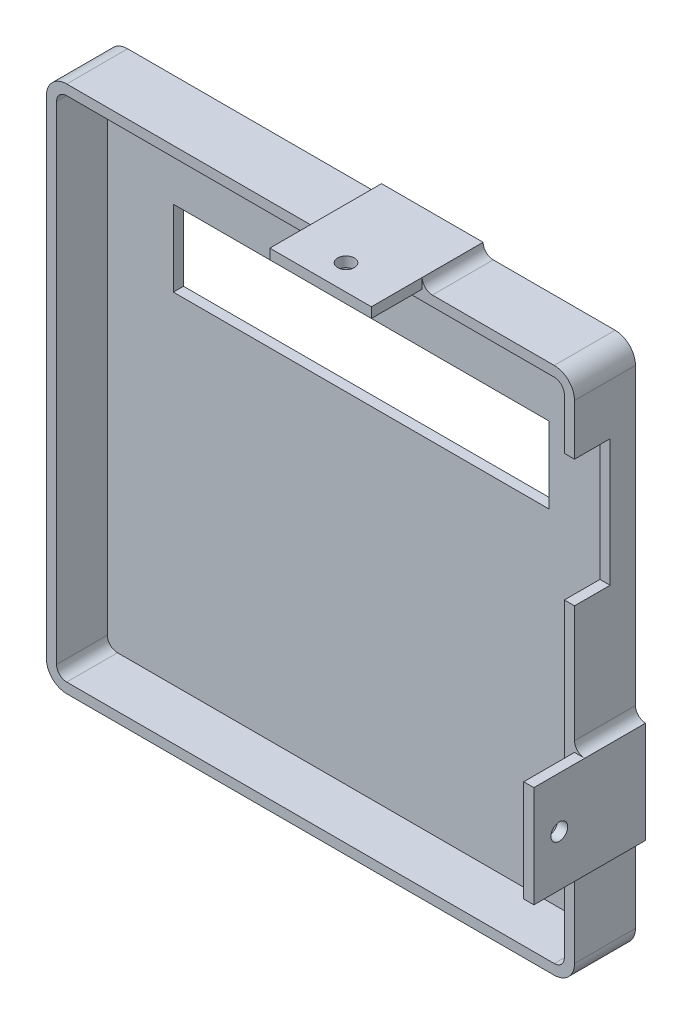
SolidWorks part; units mm, degrees
ref_plane "前视基准面" through (0, 0, 0) normal (0, 0, 1) x (1, 0, 0)
ref_plane "上视基准面" through (0, 0, 0) normal (0, 1, 0) x (1, 0, 0)
ref_plane "右视基准面" through (0, 0, 0) normal (1, 0, 0) x (0, 0, -1)
sketch "草图1" plane through (0, 0, 0) normal (0, 0, 1) x (1, 0, 0)
  line L1 (4, 0) -> (100, 0)
  line L2 (0, 4) -> (0, 100)
  line L3 (4, 104) -> (100, 104)
  line L4 (104, 4) -> (104, 100)
  arc A0 (100, 0) -> (104, 4) centre (100, 4) ccw
  arc A1 (100, 104) -> (104, 100) centre (100, 100) cw
  arc A2 (0, 100) -> (4, 104) centre (4, 100) cw
  arc A3 (4, 0) -> (0, 4) centre (4, 4) cw
  point P7 (104, 0)
  point P12 (0, 104)
  point P15 (0, 0)
  dimension "D3" = 4
  dimension "D1" = 104
  dimension "D2" = 104
extrude "凸台-拉伸2" add sketch "草图1" along normal blind 2
sketch "草图4" plane through (0, 0, 2) normal (0, 0, 1) x (1, 0, 0)
  line L4 (104, 4) -> (104, 100)
  line L5 (100, 104) -> (4, 104)
  line L6 (0, 100) -> (0, 4)
  line L7 (4, 0) -> (100, 0)
  line L8 (104, 4) -> (104, 100)
  line L9 (100, 104) -> (4, 104)
  line L10 (0, 100) -> (0, 4)
  line L11 (4, 0) -> (100, 0)
  line L16 (102, 4) -> (102, 100)
  line L17 (100, 102) -> (4, 102)
  line L18 (2, 100) -> (2, 4)
  line L19 (4, 2) -> (100, 2)
  line L20 (102, 4) -> (102, 100)
  line L21 (100, 102) -> (4, 102)
  line L22 (2, 100) -> (2, 4)
  line L23 (4, 2) -> (100, 2)
  arc A4 (100, 0) -> (104, 4) centre (100, 4) ccw
  arc A5 (104, 100) -> (100, 104) centre (100, 100) ccw
  arc A6 (4, 104) -> (0, 100) centre (4, 100) ccw
  arc A7 (0, 4) -> (4, 0) centre (4, 4) ccw
  arc A8 (100, 0) -> (104, 4) centre (100, 4) ccw
  arc A9 (104, 100) -> (100, 104) centre (100, 100) ccw
  arc A10 (4, 104) -> (0, 100) centre (4, 100) ccw
  arc A11 (0, 4) -> (4, 0) centre (4, 4) ccw
  arc A16 (100, 2) -> (102, 4) centre (100, 4) ccw
  arc A17 (102, 100) -> (100, 102) centre (100, 100) ccw
  arc A18 (4, 102) -> (2, 100) centre (4, 100) ccw
  arc A19 (2, 4) -> (4, 2) centre (4, 4) ccw
  arc A20 (100, 2) -> (102, 4) centre (100, 4) ccw
  arc A21 (102, 100) -> (100, 102) centre (100, 100) ccw
  arc A22 (4, 102) -> (2, 100) centre (4, 100) ccw
  arc A23 (2, 4) -> (4, 2) centre (4, 4) ccw
  dimension "D1" = 0
  dimension "D2" = 2
extrude "凸台-拉伸3" add sketch "草图4" along normal blind 10
sketch "草图5" plane through (104, 0, 0) normal (1, 0, 0) x (0, 0, -1)
  line L0 (-12, 4) -> (-12, 100) construction
  line L1 (-12, 90) -> (-5, 90)
  line L2 (-12, 90) -> (-12, 65)
  line L3 (-12, 65) -> (-5, 65)
  line L4 (-5, 90) -> (-5, 65)
  line L5 (-12, 100) -> (0, 100) construction
  dimension "D1" = 10
  dimension "D2" = 25
  dimension "D3" = 7
extrude "切除-拉伸1" cut sketch "草图5" against normal blind 10
sketch "草图6" plane through (0, 0, 0) normal (0, 0, -1) x (-1, 0, 0)
  line L0 (-100, 104) -> (-4, 104) construction
  line L1 (-15, 69) -> (-89, 69)
  line L2 (-15, 69) -> (-15, 84)
  line L3 (-15, 84) -> (-89, 84)
  line L4 (-89, 69) -> (-89, 84)
  line L5 (0, 100) -> (0, 4) construction
  line L6 (-104, 4) -> (-104, 100) construction
  dimension "D1" = 20
  dimension "D2" = 15
  dimension "D3" = 15
  dimension "D4" = 15
extrude "切除-拉伸2" cut sketch "草图6" against normal blind 10
sketch "草图7" plane through (0, 0, 0) normal (0, 0, -1) x (-1, 0, 0)
  line L0 (-100, 104) -> (-4, 104) construction
  line L1 (-74, 104) -> (-54, 104)
  line L2 (-74, 104) -> (-74, 106)
  line L3 (-74, 106) -> (-54, 106)
  line L4 (-54, 104) -> (-54, 106)
  line L5 (-104, 4) -> (-104, 100) construction
  line L6 (-4, 0) -> (-100, 0) construction
  line L7 (-104, 40) -> (-106, 40)
  line L8 (-104, 40) -> (-104, 20)
  line L9 (-104, 20) -> (-106, 20)
  line L10 (-106, 40) -> (-106, 20)
  dimension "D1" = 20
  dimension "D2" = 30
  dimension "D3" = 2
  dimension "D4" = 20
  dimension "D5" = 20
  dimension "D6" = 2
extrude "凸台-拉伸4" add sketch "草图7" against normal blind 22
sketch "草图8" plane through (106, 0, 0) normal (1, 0, 0) x (0, 0, -1)
  line L0 (-22, 20) -> (0, 20) construction
  line L1 (-22, 40) -> (-22, 20) construction
  circle A0 centre (-17, 30) radius 1.65
  dimension "D3" = 3.3
  dimension "D1" = 10
  dimension "D2" = 5
extrude "切除-拉伸3" cut sketch "草图8" against normal blind 22
sketch "草图10" plane through (0, 106, 0) normal (0, 1, 0) x (1, 0, 0)
  line L0 (74, -22) -> (74, 0) construction
  line L1 (54, -22) -> (74, -22) construction
  circle A0 centre (64, -17) radius 1.65
  dimension "D3" = 3.3
  dimension "D1" = 10
  dimension "D2" = 5
extrude "切除-拉伸4" cut sketch "草图10" against normal blind 22
fillet "圆角1" radius 2 4 edges at (54, 104, 6) (74, 104, 6) (104, 20, 6) (104, 40, 6)
